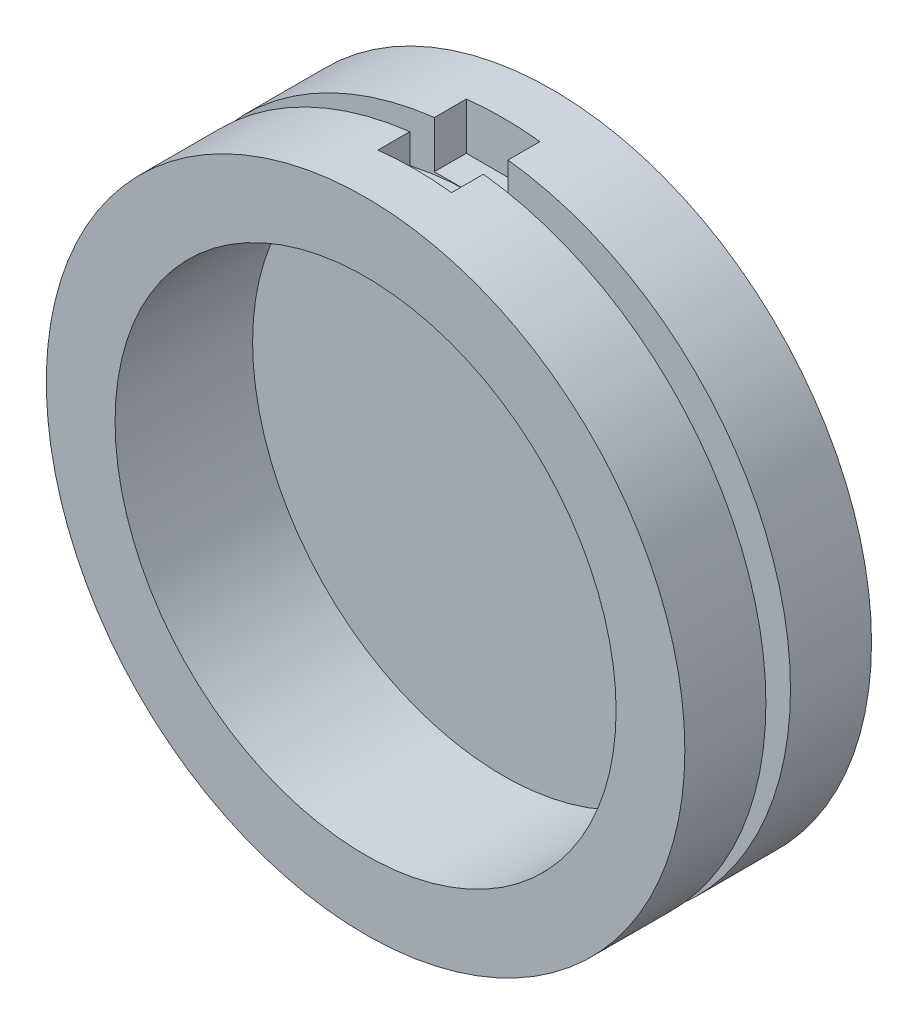
SolidWorks part; units mm, degrees
ref_plane "Front Plane" through (0, 0, 0) normal (0, 0, 1) x (1, 0, 0)
ref_plane "Top Plane" through (0, 0, 0) normal (0, 1, 0) x (1, 0, 0)
ref_plane "Right Plane" through (0, 0, 0) normal (1, 0, 0) x (0, 0, -1)
sketch "Sketch2" plane through (0, 0, 0) normal (1, 0, 0) x (0, 0, -1)
  line L0 (0, 0) -> (0, 32.5)
  line L1 (0, 32.5) -> (-8.25, 32.5)
  line L2 (-19, 32.5) -> (-19, 25.5)
  line L3 (-19, 25.5) -> (-5, 25.5)
  line L4 (-5, 25.5) -> (-5, 0)
  line L5 (-5, 0) -> (0, 0)
  line L6 (-8.25, 32.5) -> (-8.25, 27.5)
  line L7 (-8.25, 27.5) -> (-10.75, 27.5)
  line L8 (-10.75, 27.5) -> (-10.75, 32.5)
  line L9 (-10.75, 32.5) -> (-19, 32.5)
  dimension "D1" = 19
  dimension "D2" = 32.5
  dimension "D3" = 7
  dimension "D4" = 5
  dimension "D5" = 2.5
  dimension "D6" = 8.25
  dimension "D7" = 5
revolve "Revolve1" add sketch "Sketch2" angle 360 about L5
ref_plane "Plane1" through (0, 32.5, 0) normal (0, 1, 0) x (1, 0, 0)
sketch "Sketch7" plane through (0, 32.5, 0) normal (0, 1, 0) x (1, 0, 0)
  line L1 (-3.75, -14) -> (3.75, -14)
  line L2 (-3.75, -14) -> (-3.75, -5)
  line L3 (-3.75, -5) -> (3.75, -5)
  line L4 (3.75, -14) -> (3.75, -5)
  line L5 (-3.75, -9.5) -> (3.75, -9.5) construction
  line L6 (32.5, 0) -> (-32.5, 0) construction
  line L7 (0, -5) -> (0, 0) construction
  dimension "D1" = 9.5
  dimension "D2" = 9
  dimension "D3" = 7.5
extrude "Cut-Extrude1" cut sketch "Sketch7" against normal blind 5
mirror "Mirror1" about plane through (0, 0, 0) normal (0, 1, 0) of "Cut-Extrude1"
